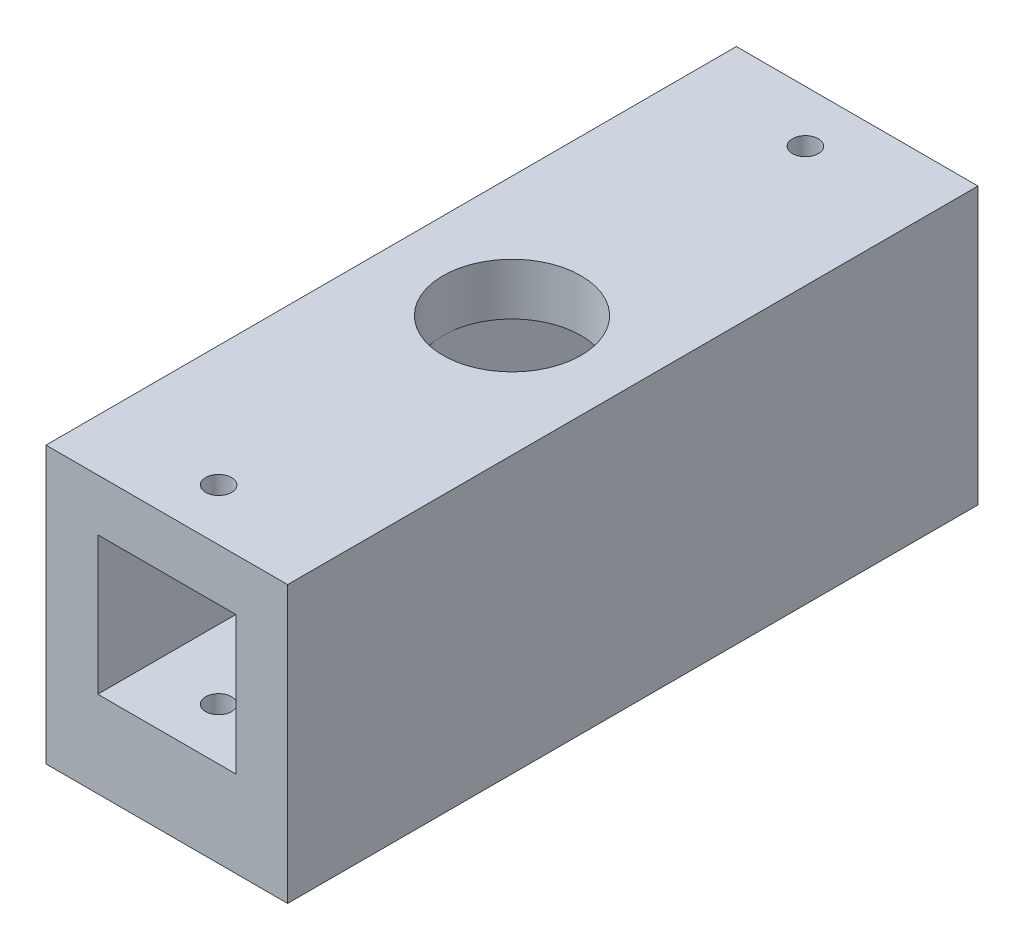
SolidWorks part; units mm, degrees
ref_plane "Front Plane" through (0, 0, 0) normal (0, 0, 1) x (1, 0, 0)
ref_plane "Top Plane" through (0, 0, 0) normal (0, 1, 0) x (1, 0, 0)
ref_plane "Right Plane" through (0, 0, 0) normal (1, 0, 0) x (0, 0, -1)
sketch "Sketch1" plane through (0, 0, 0) normal (0, 0, 1) x (1, 0, 0)
  line L0 (-7, 7) -> (-7, -7)
  line L1 (-4, 4) -> (4, 4)
  line L2 (-4, 4) -> (-4, -4)
  line L3 (-4, -4) -> (4, -4)
  line L4 (4, 4) -> (4, -4)
  line L5 (-4, 4) -> (4, -4) construction
  line L6 (-4, -4) -> (4, 4) construction
  line L8 (7, 7) -> (7, -7)
  line L9 (-7, 7) -> (7, 7)
  line L10 (7, -7) -> (7, -9)
  line L11 (7, -9) -> (-7, -9)
  line L12 (-7, -9) -> (-7, -7)
  line L14 (-7, -7) -> (7, -7) construction
  point P0 (0, 0)
  dimension "D1" = 8
  dimension "D2" = 8
  dimension "D4" = 2
  dimension "D3" = 3
extrude "Boss-Extrude1" add sketch "Sketch1" along normal blind 40
sketch "Sketch2" plane through (0, -4, 0) normal (0, 1, 0) x (1, 0, 0)
  line L0 (-4, 0) -> (4, 0) construction
  circle A0 centre (0, -20) radius 2.75
  circle A1 centre (0, -20) radius 4
  point P6 (0, 0)
  dimension "D1" = 5.5
  dimension "D3" = 20
  dimension "D2" = 8
extrude "Cut-Extrude1" cut sketch "Sketch2" against normal blind 18 contours A0
sketch "Sketch4" plane through (0, 7, 0) normal (0, 1, 0) x (1, 0, 0)
  line L0 (7, 0) -> (-7, 0) construction
  line L1 (7, -40) -> (-7, -40) construction
  circle A0 centre (0, -3) radius 0.75
  circle A1 centre (0, -37) radius 0.75
  dimension "D2" = 1.5
  dimension "D3" = 1.5
  dimension "D1" = 3
  dimension "D4" = 3
extrude "Cut-Extrude2" cut sketch "Sketch4" against normal blind 19
extrude "Cut-Extrude3" cut sketch "Sketch2<5>" against normal blind 2 and the other way blind 30 contours A1
sketch "Sketch2<5>" plane through (0, -4, 0) normal (0, 1, 0) x (1, 0, 0) same geometry as "Sketch2"
sketch "Sketch5" plane through (-7, 0, 0) normal (-1, 0, 0) x (0, 0, 1)
  line L0 (40, -9) -> (0, -9) construction
  line L1 (15, -9) -> (25, -9)
  line L2 (15, -9) -> (15, -6)
  line L3 (15, -6) -> (25, -6)
  line L4 (25, -9) -> (25, -6)
  line L6 (0, 7) -> (0, -9) construction
  dimension "D1" = 10
  dimension "D2" = 3
  dimension "D3" = 15
